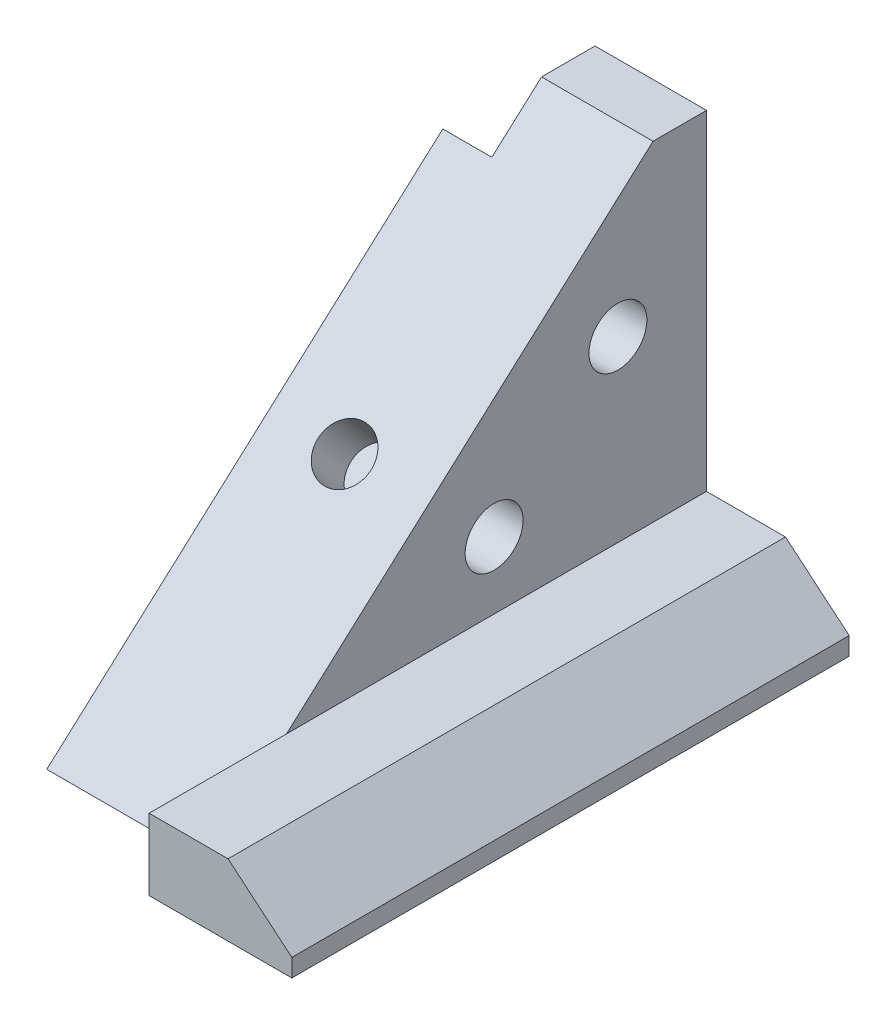
SolidWorks part; units mm, degrees
ref_plane "Front Plane" through (0, 0, 0) normal (0, 0, 1) x (1, 0, 0)
ref_plane "Top Plane" through (0, 0, 0) normal (0, 1, 0) x (1, 0, 0)
ref_plane "Right Plane" through (0, 0, 0) normal (1, 0, 0) x (0, 0, -1)
sketch "Sketch1" plane through (0, 0, 0) normal (1, 0, 0) x (0, 0, -1)
  line L0 (0, 16) -> (0, 90)
  line L1 (0, 0) -> (-125, 0)
  line L2 (0, 0) -> (0, 16)
  line L3 (0, 16) -> (-125, 16)
  line L4 (-125, 0) -> (-125, 16)
  line L5 (0, 90) -> (-12, 90)
  line L6 (-12, 90) -> (-94.1853, 16)
  line L7 (-6.2198, 68.2918) -> (-55.4098, 24.001) construction
  line L8 (-94.1853, 16) -> (-111.9551, 0)
  circle A0 centre (-19.8713, 56) radius 6.5
  circle A1 centre (-47.6366, 31) radius 6.5
  dimension "D1" = 42
  dimension "D5" = 13
  dimension "D6" = 13
  dimension "D2" = 40
  dimension "D3" = 15
  dimension "D4" = 125
  dimension "D7" = 12
  dimension "D8" = 20
  dimension "D9" = 90
  dimension "D10" = 16
extrude "Boss-Extrude1" add sketch "Sketch1" along normal blind 36 contours L5 L6 L3 L0 A0 A1 | L3 L8 L1 L2 region at (0, 43.4509, 31.709) region at (0, 7.7701, 51.6628)
extrude "Boss-Extrude2" add sketch "Sketch1<4>" along normal blind 32 from offset 36 contours L8 L3 L4 L1 | L3 L8 L1 L2 region at (0, 7.7701, 51.6628) region at (0, 9.0804, 113.4352)
sketch "Sketch1<4>" plane through (0, 0, 0) normal (1, 0, 0) x (0, 0, -1) same geometry as "Sketch1"
sketch "Sketch3" plane through (0, 55.6709, 50.1263) normal (0, 0.7431, 0.6691) x (1, 0, 0)
  line L0 (11, 60.2218) -> (11, 36.304)
  line L1 (36, 60.2218) -> (0, 60.2218) construction
  line L2 (11, 36.304) -> (0, 36.304)
  line L3 (0, 51.304) -> (0, -83.1989) construction
  line L4 (36, -83.1989) -> (0, -83.1989) construction
  line L5 (36, 51.304) -> (0, 51.304) construction
  line L6 (11, 60.2218) -> (0, 60.2218)
  line L7 (0, 60.2218) -> (0, 36.304)
  circle A0 centre (17, -16.1989) radius 6
  point P11 (5.5, 36.304)
  line M2 (0, 51.304) -> (0, -83.1989)
  line M6 (36, 51.304) -> (0, 51.304)
  dimension "D1" = 17
  dimension "D2" = 67
  dimension "D3" = 11
  dimension "D4" = 15
extrude "Cut-Extrude1" cut sketch "Sketch3" against normal up to next contours L2 L0 M6 M2 | L6 L7 L0 M6 region at (5.5, 92.9836, 8.6864) region at (5.5, 84.9815, 17.5736)
extrude "Cut-Extrude3" cut sketch "Sketch3<6>" against normal blind 11 contours A0 region at (17, 44.8318, 62.1644)
sketch "Sketch3<6>" plane through (0, 55.6709, 50.1263) normal (0, 0.7431, 0.6691) x (1, 0, 0) same geometry as "Sketch3"
sketch "Sketch4" plane through (0, 0, 125) normal (0, 0, 1) x (1, 0, 0)
  line L0 (68, 4) -> (53.699, 16)
  line L1 (68, 0) -> (68, 16) construction
  line L2 (68, 16) -> (36, 16) construction
  line L3 (68, 0) -> (36, 0) construction
  line M4 (68, 0) -> (68, 16)
  line M5 (68, 16) -> (36, 16)
  dimension "D1" = 4
  dimension "D2" = 50
extrude "Cut-Extrude4" cut sketch "Sketch4" against normal through all and the other way through all contours L0 M4 M5 region at (63.233, 12, 125)
